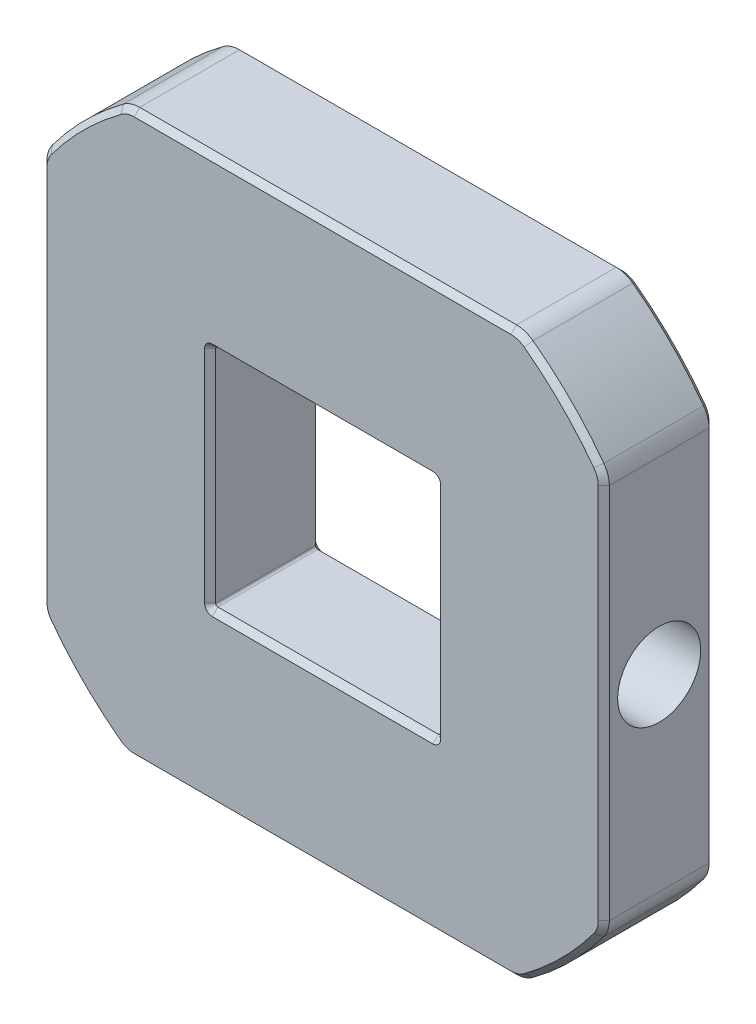
SolidWorks part; units mm, degrees
ref_plane "Front" through (0, 0, 0) normal (0, 0, 1) x (1, 0, 0)
ref_plane "Top" through (0, 0, 0) normal (0, 1, 0) x (1, 0, 0)
ref_plane "Right" through (0, 0, 0) normal (1, 0, 0) x (0, 0, -1)
sketch "Skizze1" plane through (0, 0, 0) normal (0, 0, 1) x (1, 0, 0)
  line L0 (17.8076, 25.375) -> (-17.8076, 25.375)
  line L1 (-10.15, -10.15) -> (10.15, -10.15)
  line L2 (-10.15, -10.15) -> (-10.15, 10.15)
  line L3 (-10.15, 10.15) -> (10.15, 10.15)
  line L4 (10.15, -10.15) -> (10.15, 10.15)
  line L5 (-10.15, -10.15) -> (10.15, 10.15) construction
  line L6 (-10.15, 10.15) -> (10.15, -10.15) construction
  line L7 (25.375, 17.8076) -> (25.375, -17.8076)
  line L8 (-17.8076, -25.375) -> (17.8076, -25.375)
  line L9 (-25.375, -17.8076) -> (-25.375, 17.8076)
  arc A0 (-25.375, -17.8076) -> (-17.8076, -25.375) centre (0, 0) ccw
  arc A1 (-17.8076, 25.375) -> (-25.375, 17.8076) centre (0, 0) ccw
  arc A2 (25.375, 17.8076) -> (17.8076, 25.375) centre (0, 0) ccw
  arc A3 (17.8076, -25.375) -> (25.375, -17.8076) centre (0, 0) ccw
  dimension "D1" = 62
  dimension "D2" = 20.3
  dimension "D3" = 50.75
extrude "Aufsatz-Linear austragen1" add sketch "Skizze1" along normal blind 10
fillet "Verrundung1" radius 0.2 4 edges at (10.15, -10.15, 5) (-10.15, -10.15, 5) (-10.15, 10.15, 5) (10.15, 10.15, 5)
fillet "Verrundung2" radius 2.5 8 edges at (17.8076, 25.375, 5) (25.375, 17.8076, 5) (25.375, -17.8076, 5) (17.8076, -25.375, 5) (-17.8076, -25.375, 5) (-25.375, -17.8076, 5) (-25.375, 17.8076, 5) (-17.8076, 25.375, 5)
sketch "Skizze2" plane through (25.375, 0, 0) normal (1, 0, 0) x (0, 0, -1)
  line L0 (0, 0) -> (-10, 0) construction
  line L1 (-10, -16.9995) -> (-10, 16.9995) construction
  circle A0 centre (-5, 0) radius 2.3
  dimension "D1" = 4.6
extrude "Schnitt-Linear austragen1" cut sketch "Skizze2" against normal up to next
sketch "Sketch1" plane through (-25.375, 0, 0) normal (-1, 0, 0) x (0, 0, 1)
  circle A0 centre (5, 0) radius 3.75
  dimension "D1" = 7.5
extrude "Cut-Extrude1" [suppressed] cut sketch "Sketch1" against normal offset from surface (8.025 mm away) 7.2 up to face at (-10.15, 0, 5)
extrude "Cut-Extrude2" cut sketch "Sketch1<2>" along normal offset from surface (8.025 mm away) 7.2 from surface up to face at (10.15, 0, 7.3) starting at face at (25.375, 2.3, 5)
sketch "Sketch1<2>" plane through (-25.375, 0, 0) normal (-1, 0, 0) x (0, 0, 1) same geometry as "Sketch1"
chamfer "Fase2" distance 0.5 angle 45 50 edges at (10.15, 0, 7.3) (-10.0914, 10.0914, 10) (-10.15, 0, 10) (-10.0914, -10.0914, 10) (0, -10.15, 10) (10.0914, -10.0914, 10) (10.15, 0, 10) (10.0914, 10.0914, 10) (0, 10.15, 10) (25.2484, 17.7849, 10) (25.375, 0, 10) (25.2484, -17.7849, 10) (21.9203, -21.9203, 10) (17.7849, -25.2484, 10) (0, -25.375, 10) (-17.7849, -25.2484, 10) (-21.9203, -21.9203, 10) (-25.2484, -17.7849, 10) (-25.375, 0, 10) (-25.2484, 17.7849, 10) (-21.9203, 21.9203, 10) (-17.7849, 25.2484, 10) (0, 25.375, 10) (17.7849, 25.2484, 10) (21.9203, 21.9203, 10) (-10.0914, -10.0914, 0) (-10.15, 0, 0) (-10.0914, 10.0914, 0) (0, 10.15, 0) (10.0914, 10.0914, 0) (10.15, 0, 0) (10.0914, -10.0914, 0) (0, -10.15, 0) (-17.7849, 25.2484, 0) (-21.9203, 21.9203, 0) (-25.2484, 17.7849, 0) (-25.375, 0, 0) (-25.2484, -17.7849, 0) (-21.9203, -21.9203, 0) (-17.7849, -25.2484, 0) (0, -25.375, 0) (17.7849, -25.2484, 0) (21.9203, -21.9203, 0) (25.2484, -17.7849, 0) (25.375, 0, 0) (25.2484, 17.7849, 0) (21.9203, 21.9203, 0) (17.7849, 25.2484, 0) (0, 25.375, 0) (17.35, 0, 7.3)
